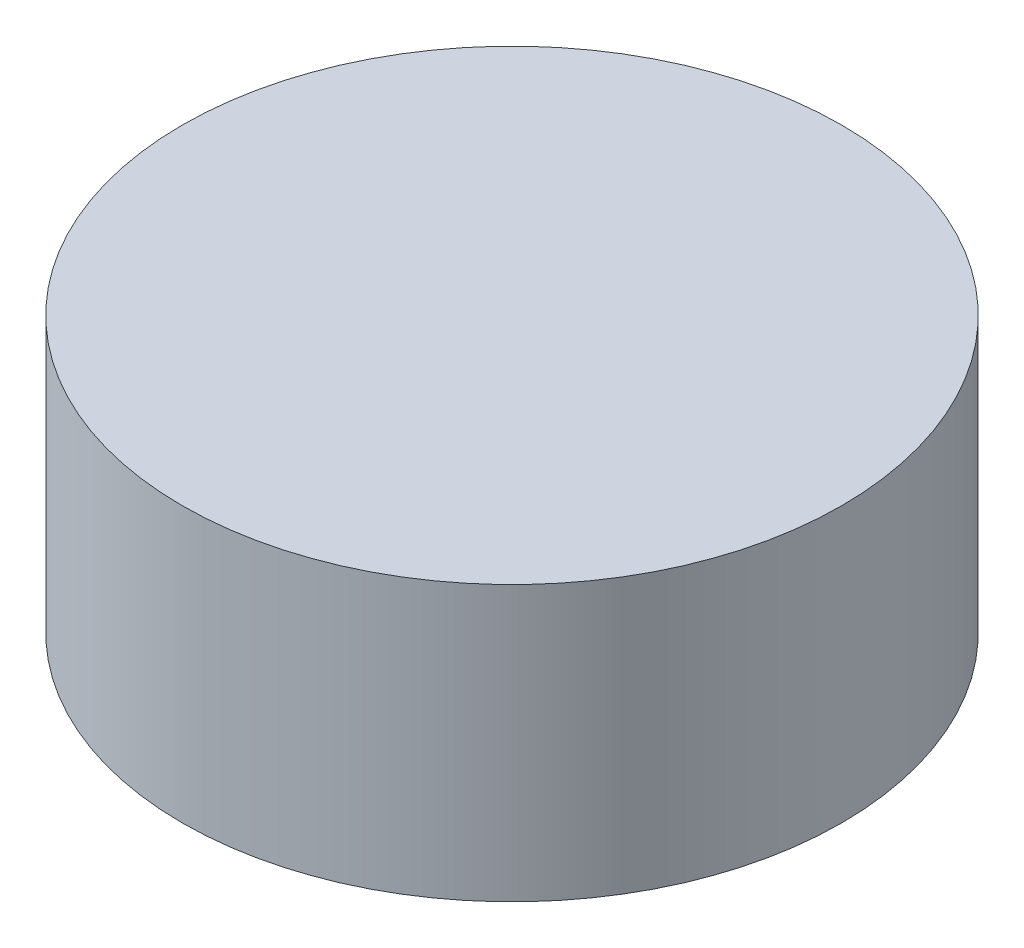
SolidWorks part; units mm, degrees
ref_plane "Front plane" through (0, 0, 0) normal (0, 0, 1) x (1, 0, 0)
ref_plane "Top plane" through (0, 0, 0) normal (0, 1, 0) x (1, 0, 0)
ref_plane "Right plane" through (0, 0, 0) normal (1, 0, 0) x (0, 0, -1)
ref_axis "Axis X" through (0, 0, 0) along (1, 0, 0)
ref_axis "Axis Y" through (0, 0, 0) along (0, 1, 0)
ref_axis "Axis Z" through (0, 0, 0) along (0, 0, 1)
sketch "Sketch1" plane through (0, 0, 0) normal (0, 1, 0) x (1, 0, 0)
  circle A0 centre (0, 0) radius 3
  dimension "D1" = 6
extrude "Extrude1" add sketch "Sketch1" along normal blind 2.5
equation "\"print_offset\" = 0.6"
equation "\"flague_diameter\"= 104"
equation "\"mounting_diameter\"= 80"
equation "\"cable_diameter\"= 2"
equation "\"bearing_d1\"= 7.7"
equation "\"bearing_d2\"= 15.9"
equation "\"bearing_h\"= 3.9"
equation "\"magnet_diameter\"= 6"
equation "\"magnet_heigh\"= 2.5"
equation "\"screw5_diameter\"= 5"
equation "\"screw5_diameter_hh\"= 8.4"
equation "\"screw5_heigh\"= 40"
equation "\"screw5_heigh_hh\"= 4.8"
equation "\"screw2_diameter\"= 1.9"
equation "\"screw2_diameter_hh\"= 3.5"
equation "\"screw2_heigh\"= 8"
equation "\"screw2_heigh_hh\"= 2"
equation "\"screw5_diameter_hex\"= 3.8"
equation "\"nut5_diameter\"= 7.8"
equation "\"nut5_heigh\"= 4"
equation "\"nut2_diameter\"= 4"
equation "\"nut2_heigh\"= 2"
equation "\"flague_heigh\"= 8"
equation "\"sitting_screws\"=4"
equation "\"cable_mount_distance\"= 10"
equation "\"distance_to_the_profile\"= 15' "
equation "\"profile_width\"= 20"
equation "\"D1@Sketch1\"=\"magnet_diameter\""
equation "\"D1@Extrude1\"=\"magnet_heigh\""
